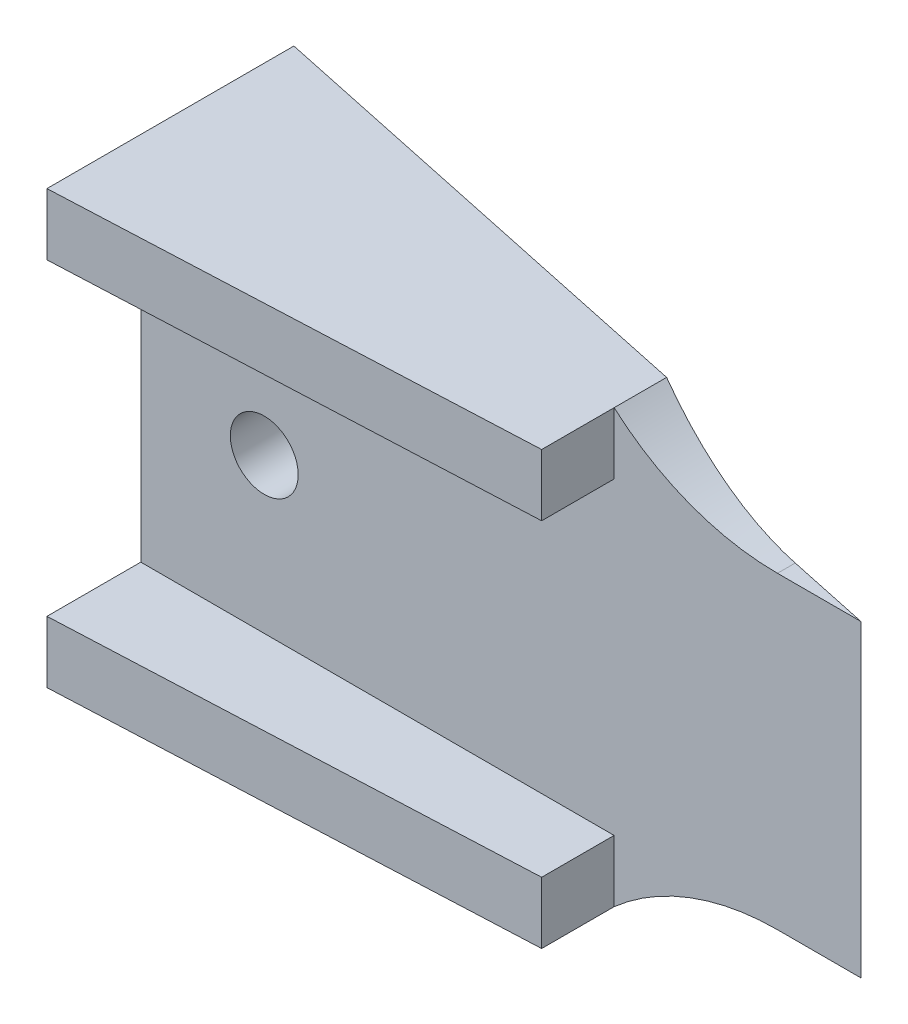
SolidWorks part; units mm, degrees
ref_plane "前视基准面" through (0, 0, 0) normal (0, 0, 1) x (1, 0, 0)
ref_plane "上视基准面" through (0, 0, 0) normal (0, 1, 0) x (1, 0, 0)
ref_plane "右视基准面" through (0, 0, 0) normal (1, 0, 0) x (0, 0, -1)
sketch "草图2" plane through (0, 0, 0) normal (0, 1, 0) x (1, 0, 0)
  line L0 (0, 0) -> (35, 0)
  line L1 (0, 0) -> (0, 7.4395)
  line L2 (0, 7.4395) -> (35, 0)
  dimension "D1" = 35
  dimension "D2" = 12
extrude "凸台-拉伸1" add sketch "草图2" along normal blind 15
ref_plane "基准面1" through (0, 0, -7.4395) normal (0, 0, 1) x (1, 0, 0)
sketch "草图3" plane through (0, 0, -7.4395) normal (0, 0, 1) x (1, 0, 0)
  line L0 (0, 7.5) -> (6, 7.5) construction
  line L1 (0, 15) -> (0, 0) construction
  circle A0 centre (6, 7.5) radius 6.5
  dimension "D2" = 13
  dimension "D1" = 6
extrude "切除-拉伸2" cut sketch "草图3" along normal blind 3
sketch "草图4" plane through (0, 0, -4.4395) normal (0, 0, -1) x (-1, 0, 0)
  circle A0 centre (-6, 7.5) radius 1.65
  dimension "D1" = 3.3
extrude "切除-拉伸3" cut sketch "草图4" against normal through all
sketch "草图6" plane through (0, 15, 0) normal (0, 1, 0) x (1, 0, 0)
  line L0 (0, 7.4395) -> (0, -4.5605)
  line L4 (35, 0) -> (23, 0) construction
  line L5 (0, 0) -> (35, 0) construction
  line L6 (23, 0) -> (23, 2.5507) construction
  line L7 (35, 0) -> (0, 7.4395) construction
  line L8 (0, -4.5605) -> (23, -3.5205)
  line L9 (23, -3.5205) -> (23, 2.5507)
  line L10 (23, 2.5507) -> (0, 7.4395)
  dimension "D1" = 12
  dimension "D2" = 12
extrude "凸台-拉伸2" add sketch "草图6" along normal blind 3
ref_plane "基准面2" through (0, 7.5, 0) normal (0, -1, 0) x (-1, 0, 0)
mirror "镜向1" about plane through (0, 7.5, 0) normal (0, -1, 0) of "凸台-拉伸2"
fillet "圆角1" radius 12 2 edges at (23, 0, -1.2753) (23, 15, -1.2753)
